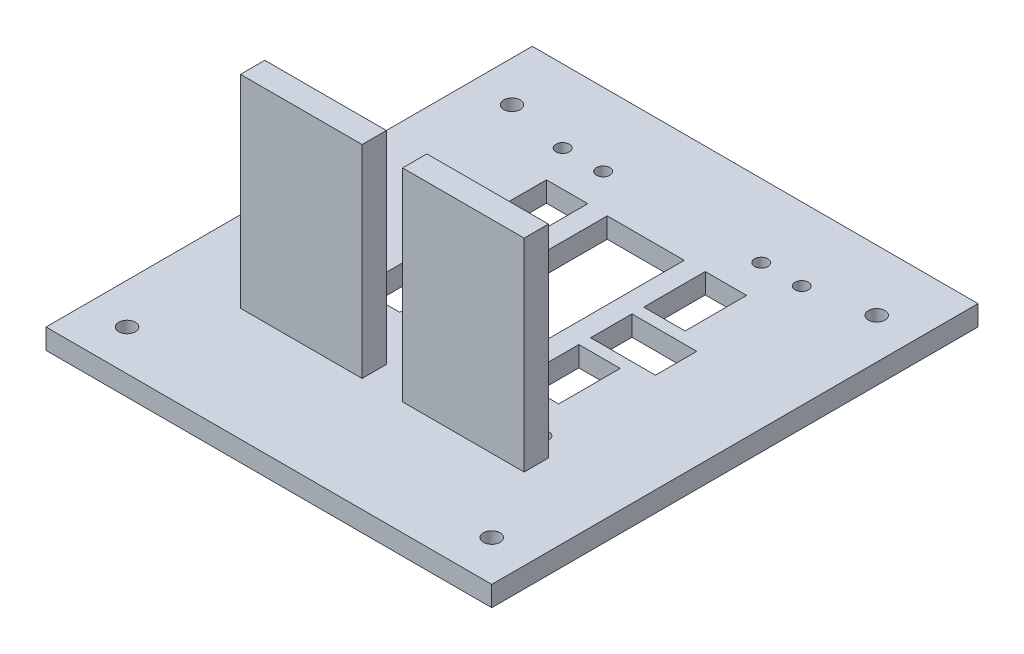
SolidWorks part; units mm, degrees
ref_plane "Front Plane" through (0, 0, 0) normal (0, 0, 1) x (1, 0, 0)
ref_plane "Top Plane" through (0, 0, 0) normal (0, 1, 0) x (1, 0, 0)
ref_plane "Right Plane" through (0, 0, 0) normal (1, 0, 0) x (0, 0, -1)
sketch "Sketch1" plane through (0, 0, 0) normal (0, 1, 0) x (1, 0, 0)
  line L0 (0, 0) -> (9.5, 0) construction
  line L1 (-55, 70) -> (55, 70)
  line L2 (-55, 70) -> (-55, -70)
  line L3 (-55, -70) -> (55, -70)
  line L4 (55, 70) -> (55, -70)
  line L5 (-55, 70) -> (55, -70) construction
  line L6 (-55, -70) -> (55, 70) construction
  line L7 (-9.5, 23) -> (9.5, 23)
  line L8 (-9.5, 23) -> (-9.5, -23)
  line L9 (-9.5, -23) -> (9.5, -23)
  line L10 (9.5, 23) -> (9.5, -23)
  line L11 (-9.5, 23) -> (9.5, -23) construction
  line L12 (-9.5, -23) -> (9.5, 23) construction
  line L14 (0, 0) -> (0, 35.7746) construction
  line L17 (-55, -70) -> (-20, -70)
  line L18 (-55, -70) -> (-55, -31.75)
  line L22 (-55, 70) -> (55, 70)
  line L23 (-55, 70) -> (-55, 50)
  line L24 (-55, 50) -> (55, 50)
  line L25 (55, 70) -> (55, 50)
  line L31 (-55, 31.75) -> (-55, -31.75)
  line L35 (55, 31.75) -> (55, -31.75)
  line L36 (-20, 70) -> (20, 70)
  line L40 (-20, -70) -> (20, -70)
  line L46 (2.5, -70) -> (42.5, -70)
  circle A1 centre (29.5, 32) radius 1.65
  circle A2 centre (19.5, 32) radius 1.65
  circle A3 centre (19.5, -32) radius 1.65
  circle A4 centre (29.5, -32) radius 1.65
  circle A5 centre (-29.5, -32) radius 1.65
  circle A6 centre (-19.5, -32) radius 1.65
  circle A7 centre (-19.5, 32) radius 1.65
  circle A8 centre (-29.5, 32) radius 1.65
  point P0 (0, 0)
  point P6 (0, 0)
  point P13 (0, 0)
  dimension "D5" = 9
  dimension "D8" = 20
  dimension "D9" = 20
  dimension "D6" = 3.3
  dimension "D1" = 140
  dimension "D2" = 110
  dimension "D3" = 46
  dimension "D4" = 19
  dimension "D7" = 2
extrude "Boss-Extrude3" add sketch "Sketch1" along normal blind 5 contours L4 L1 L2 L3 A7 A6 A5 A3 A2 A1 L7 L10 L9 L8 A4 A8 region at (0, 0, -48.3721)
sketch "Sketch5" plane through (0, 0, 0) normal (0, -1, 0) x (1, 0, 0)
  line L0 (-55, 70) -> (55, 70) construction
  line L1 (-55, -50) -> (-55, 70) construction
  line L2 (-55, -50) -> (55, -50) construction
  line L3 (0, 0) -> (0, -67.3907) construction
  circle A0 centre (-45, 60) radius 2.05
  circle A1 centre (-45, -35) radius 2.05
  circle A2 centre (45, -35) radius 2.05
  circle A3 centre (45, 60) radius 2.05
  dimension "D1" = 4.1
  dimension "D3" = 10
  dimension "D4" = 4.1
  dimension "D6" = 10
  dimension "D2" = 10
  dimension "D5" = 15
extrude "Cut-Extrude2" cut sketch "Sketch5" against normal through all
sketch "Sketch9" plane through (0, 5, 0) normal (0, 1, 0) x (1, 0, 0)
  line L0 (0, 0) -> (0, -16.1548) construction
  line L1 (-9.5, 23) -> (9.5, 23)
  line L2 (-9.5, 23) -> (-9.5, -23)
  line L3 (-9.5, -23) -> (9.5, -23)
  line L4 (9.5, 23) -> (9.5, -23)
  line L5 (-9.5, 23) -> (9.5, -23) construction
  line L6 (-9.5, -23) -> (9.5, 23) construction
  line L7 (-14.5, 23.2) -> (-24.7, 23.2)
  line L8 (-14.5, 23.2) -> (-14.5, -23.2)
  line L9 (-14.5, -23.2) -> (-24.7, -23.2)
  line L10 (-24.7, 23.2) -> (-24.7, -23.2)
  line L11 (-24.7, 8) -> (-14.5, 8)
  line L12 (-24.7, -8) -> (-14.5, -8)
  line L13 (24.7, -8) -> (14.5, -8)
  line L14 (24.7, 8) -> (14.5, 8)
  line L15 (24.7, 23.2) -> (24.7, -23.2)
  line L16 (14.5, -23.2) -> (24.7, -23.2)
  line L17 (14.5, 23.2) -> (14.5, -23.2)
  line L18 (14.5, 23.2) -> (24.7, 23.2)
  point P0 (0, 0)
  dimension "D1" = 5
  dimension "D2" = 10.2
  dimension "D3" = 0.2
  dimension "D4" = 0.2
  dimension "D5" = 15.2
  dimension "D6" = 15.2
extrude "Cut-Extrude3" cut sketch "Sketch9" against normal through all contours L10 L11 L8 L7 | L12 L10 L9 L8 | L13 L17 L16 L15 | L18 L17 L14 L15 region at (-19.6, 5, -15.6) region at (-19.6, 5, 15.6) region at (19.6, 5, 15.6) region at (19.6, 5, -15.6)
sketch "Sketch6" plane through (0, 5, 0) normal (0, 1, 0) x (1, 0, 0)
  line L6 (-9.5, -23) -> (9.5, -23) construction
  line L8 (-35, -36) -> (35, -36)
  line L9 (-35, -36) -> (-35, -42)
  line L10 (-35, -42) -> (35, -42)
  line L11 (35, -36) -> (35, -42)
  line L14 (-9.5, 23) -> (-9.5, -23) construction
  line L15 (5, -36) -> (-5, -36)
  line L16 (5, -36) -> (5, -42)
  line L17 (5, -42) -> (-5, -42)
  line L18 (-5, -36) -> (-5, -42)
  line L19 (9.5, 23) -> (9.5, -23) construction
  dimension "D1" = 13
  dimension "D2" = 6
  dimension "D3" = 4.5
  dimension "D4" = 4.5
  dimension "D5" = 30
  dimension "D6" = 30
extrude "Boss-Extrude4" add sketch "Sketch6" along normal blind 50 contours L18 L8 L9 L10 | L8 L16 L10 L11 region at (-20, 5, 39) region at (20, 5, 39)
sketch "Sketch11" plane through (0, 5, 0) normal (0, 1, 0) x (1, 0, 0)
  line L0 (9.5, 23) -> (9.5, -23) construction
  line L1 (14.5, 5.1) -> (30.5, 5.1)
  line L2 (14.5, 5.1) -> (14.5, -5.1)
  line L3 (14.5, -5.1) -> (30.5, -5.1)
  line L4 (30.5, 5.1) -> (30.5, -5.1)
  line L5 (-9.5, -23) -> (9.5, -23) construction
  line L6 (-9.5, 23) -> (9.5, 23) construction
  dimension "D1" = 5
  dimension "D2" = 16
  dimension "D3" = 17.9
  dimension "D4" = 17.9
extrude "Cut-Extrude4" cut sketch "Sketch11" against normal through all
